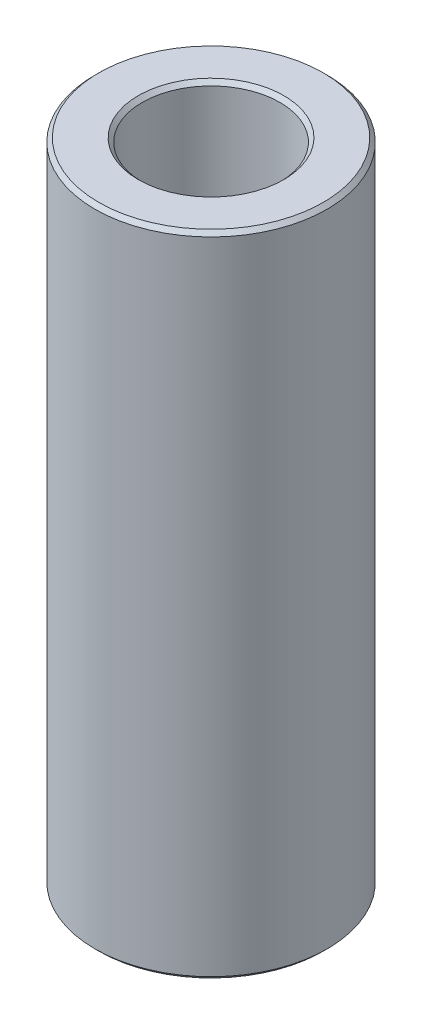
SolidWorks part; units mm, degrees
ref_plane "Front Plane" through (0, 0, 0) normal (0, 0, 1) x (1, 0, 0)
ref_plane "Top Plane" through (0, 0, 0) normal (0, 1, 0) x (1, 0, 0)
ref_plane "Right Plane" through (0, 0, 0) normal (1, 0, 0) x (0, 0, -1)
sketch "Sketch1" plane through (0, 0, 0) normal (0, 1, 0) x (1, 0, 0)
  circle A0 centre (0, 0) radius 52.5
  dimension "SLEEVE_OD" = 105
extrude "Boss-Extrude1" add sketch "Sketch1" along normal blind 293.058
sketch "Sketch2" plane through (0, 0, 0) normal (0, 1, 0) x (1, 0, 0)
  circle A0 centre (0, 0) radius 31.1287
  dimension "BORE_D" = 62.2573
extrude "Cut-Extrude1" cut sketch "Sketch2" along normal through all
chamfer "Chamfer1" distance 1.773 angle 45 4 edges at (0, 293.058, 31.1287) (0, 0, 31.1287) (0, 0, 52.5) (0, 293.058, 52.5)
